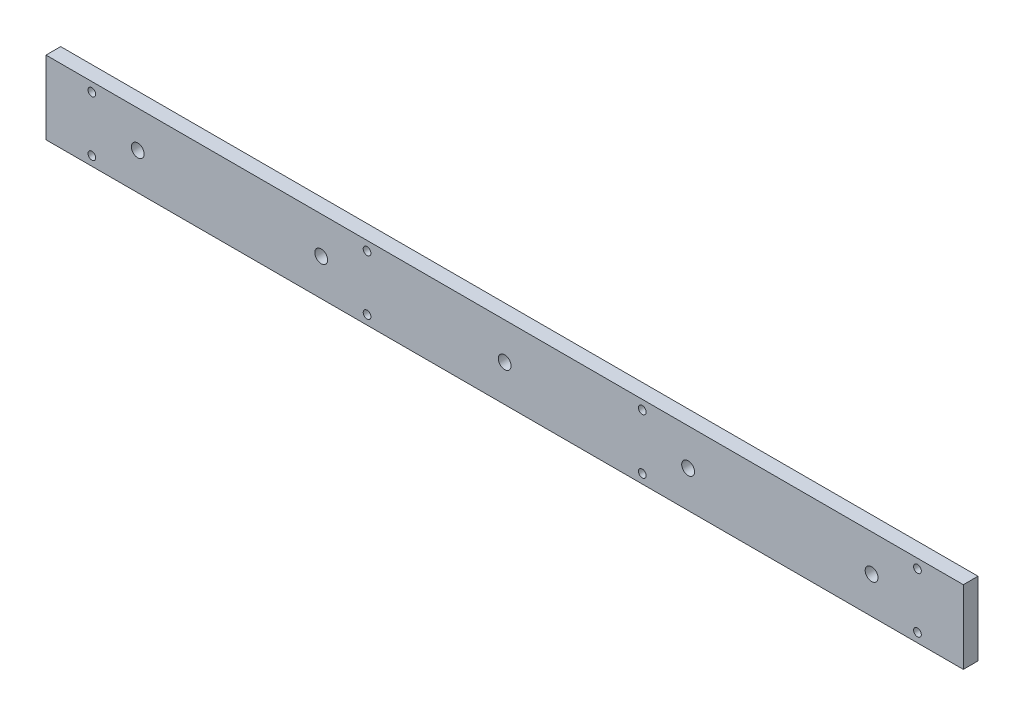
SolidWorks part; units mm, degrees
ref_plane "Plan de face" through (0, 0, 0) normal (0, 0, 1) x (1, 0, 0)
ref_plane "Plan de dessus" through (0, 0, 0) normal (0, 1, 0) x (1, 0, 0)
ref_plane "Plan de droite" through (0, 0, 0) normal (1, 0, 0) x (0, 0, -1)
sketch "Esquisse1" plane through (0, 0, 0) normal (0, 0, 1) x (1, 0, 0)
  line L1 (0, 0) -> (500, 0)
  line L2 (0, 0) -> (0, 40)
  line L3 (0, 40) -> (500, 40)
  line L4 (500, 0) -> (500, 40)
  dimension "D1" = 40
  dimension "D2" = 500
extrude "Boss.-Extru.1" add sketch "Esquisse1" along normal blind 8
sketch "Esquisse2" plane through (0, 0, 8) normal (0, 0, 1) x (1, 0, 0)
  line L0 (0, 20) -> (500, 20) construction
  line L1 (0, 40) -> (0, 0) construction
  line L2 (500, 0) -> (500, 40) construction
  line L3 (250, 20) -> (250, 0) construction
  line L4 (0, 0) -> (500, 0) construction
  line L5 (25, 35) -> (175, 35) construction
  line L6 (475, 35) -> (325, 35) construction
  line L7 (475, 5) -> (325, 5) construction
  line L8 (25, 5) -> (175, 5) construction
  circle A0 centre (250, 20) radius 3.5
  circle A1 centre (150, 20) radius 3.5
  circle A2 centre (50, 20) radius 3.5
  circle A3 centre (450, 20) radius 3.5
  circle A4 centre (350, 20) radius 3.5
  circle A5 centre (25, 35) radius 2.1
  circle A6 centre (175, 35) radius 2.1
  circle A7 centre (325, 35) radius 2.1
  circle A8 centre (475, 35) radius 2.1
  circle A9 centre (475, 5) radius 2.1
  circle A10 centre (325, 5) radius 2.1
  circle A11 centre (175, 5) radius 2.1
  circle A12 centre (25, 5) radius 2.1
  dimension "D1" = 7
  dimension "D2" = 100
  dimension "D3" = 100
  dimension "D4" = 4.2
  dimension "D5" = 150
  dimension "D6" = 150
  dimension "D7" = 30
extrude "Enlèv. mat.-Extru.1" cut sketch "Esquisse2" against normal through all both and the other way through all
